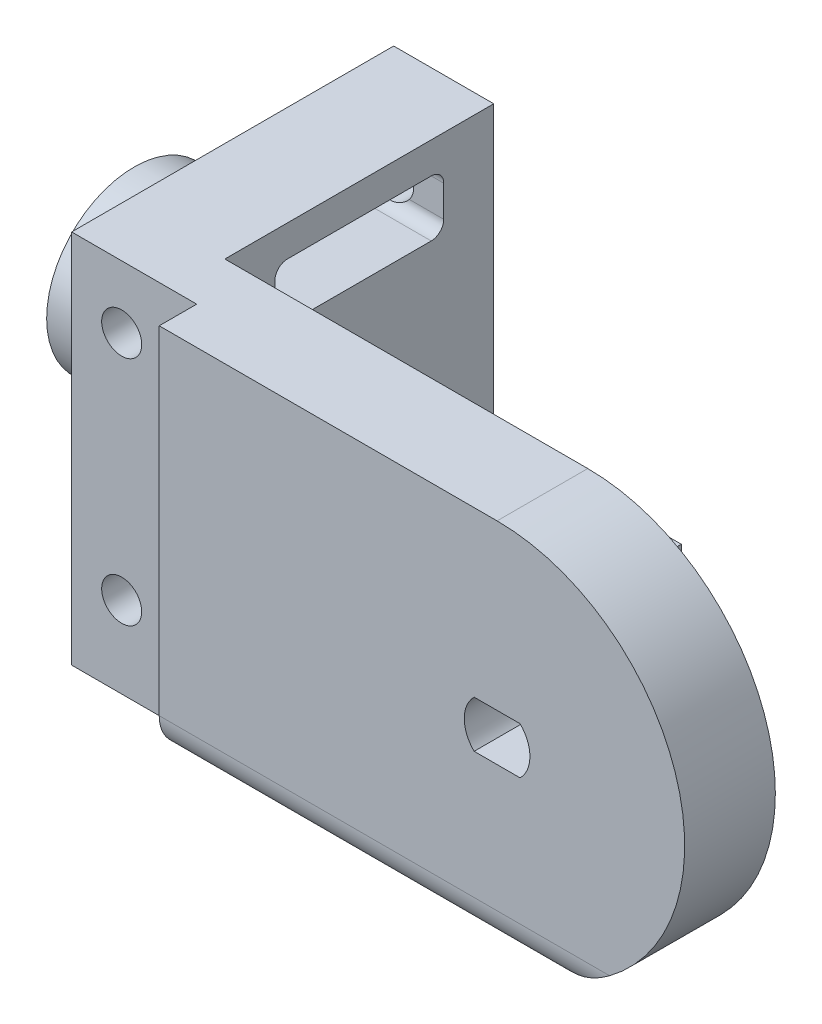
SolidWorks part; units mm, degrees
ref_plane "Front Plane" through (0, 0, 0) normal (0, 0, 1) x (1, 0, 0)
ref_plane "Top Plane" through (0, 0, 0) normal (0, 1, 0) x (1, 0, 0)
ref_plane "Right Plane" through (0, 0, 0) normal (1, 0, 0) x (0, 0, -1)
sketch "Sketch2" plane through (0, 0, -8) normal (0, 0, 1) x (1, 0, 0)
  line L0 (-25.7692, 245.1803) -> (-54.7874, 245.1803)
  line L1 (-54.7874, 245.1803) -> (-54.7874, 215.1803)
  line L2 (-54.7874, 215.1803) -> (-25.7692, 215.1803)
  arc A2 (-25.7692, 215.1803) -> (-25.7692, 245.1803) centre (-25.7692, 230.1803) ccw
  dimension "D1" = 29.0182
extrude "Boss-Extrude1" add sketch "Sketch2" along normal blind 8
sketch "Sketch3" plane through (0, 0, -28) normal (0, 0, -1) x (-1, 0, 0)
  line L3 (25.7692, 215.1803) -> (54.7874, 215.1803)
  line L4 (54.7874, 215.1803) -> (54.7874, 245.1803)
  line L5 (54.7874, 245.1803) -> (25.7692, 245.1803)
  line L6 (25.7692, 215.1803) -> (54.7874, 215.1803)
  line L7 (54.7874, 215.1803) -> (54.7874, 245.1803)
  line L8 (54.7874, 245.1803) -> (25.7692, 245.1803)
  arc A1 (25.7692, 245.1803) -> (25.7692, 215.1803) centre (25.7692, 230.1803) ccw
  arc A2 (25.7692, 245.1803) -> (25.7692, 215.1803) centre (25.7692, 230.1803) ccw
  dimension "D1" = 0
extrude "Boss-Extrude2" add sketch "Sketch3" along normal blind 8 separate body
sketch "Sketch4" plane through (-54.7874, 0, 0) normal (-1, 0, 0) x (0, 0, 1)
  line L1 (-36, 245.1803) -> (0, 245.1803)
  line L2 (-36, 245.1803) -> (-36, 215.1803)
  line L3 (-36, 215.1803) -> (0, 215.1803)
  line L4 (0, 245.1803) -> (0, 215.1803)
extrude "Boss-Extrude3" add sketch "Sketch4" along normal blind 8
sketch "Sketch5" plane through (-62.7874, 0, 0) normal (-1, 0, 0) x (0, 0, 1)
  circle A1 centre (-18, 230.1803) radius 7
  circle A2 centre (-18, 230.1803) radius 5
extrude "Boss-Extrude4" add sketch "Sketch5" along normal blind 10
chamfer "Chamfer1" distance 3 angle 45 1 edges at (-62.7874, 230.1803, -11)
sketch "Sketch6" plane through (0, 0, -36) normal (0, 0, -1) x (-1, 0, 0)
  line L0 (23.9321, 232.0553) -> (27.6063, 232.0553)
  line L1 (23.9321, 228.3053) -> (27.6063, 228.3053)
  arc A0 (23.9321, 232.0553) -> (23.9321, 228.3053) centre (25.7692, 230.1803) ccw
  arc A1 (27.6063, 228.3053) -> (27.6063, 232.0553) centre (25.7692, 230.1803) ccw
  dimension "D1" = 1.875
  dimension "D2" = 3.75
extrude "Cut-Extrude1" cut sketch "Sketch6" against normal up to surface (36 mm away) up to face at (-40.5283, 230.1803, 0)
sketch "Sketch7" plane through (-62.7874, 0, 0) normal (-1, 0, 0) x (0, 0, 1)
  line L0 (0, 215.1803) -> (0, 218.1803)
  line L1 (0, 215.1803) -> (0, 245.1803) construction
  line L2 (0, 215.1803) -> (-3, 215.1803)
  line L3 (-36, 215.1803) -> (0, 215.1803) construction
  line L4 (-18, 215.1803) -> (-18, 245.1803) construction
  line L5 (0, 245.1803) -> (-36, 245.1803) construction
  line L6 (-36, 215.1803) -> (-33, 215.1803)
  line L7 (-36, 215.1803) -> (-36, 218.1803)
  arc A0 (0, 218.1803) -> (-3, 215.1803) centre (-3, 218.1803) cw
  arc A1 (-36, 218.1803) -> (-33, 215.1803) centre (-33, 218.1803) ccw
extrude "Cut-Extrude2" cut sketch "Sketch7" against normal through all
sketch "Sketch8" plane through (0, 215.1803, 0) normal (0, -1, 0) x (1, 0, 0)
  line L0 (-54.7874, -8) -> (-25.7692, -8) construction
  line L1 (-56.7874, -28) -> (-39.7874, -28)
  line L2 (-56.7874, -28) -> (-56.7874, -8)
  line L3 (-56.7874, -8) -> (-39.7874, -8)
  line L4 (-39.7874, -28) -> (-39.7874, -8)
extrude "Boss-Extrude5" add sketch "Sketch8" against normal blind 7
sketch "Sketch10" plane through (0, 0, -28) normal (0, 0, 1) x (1, 0, 0)
  line L5 (-54.7874, 222.1803) -> (-39.7874, 222.1803)
  line L6 (-39.7874, 222.1803) -> (-39.7874, 215.1803)
  line L7 (-39.7874, 215.1803) -> (-25.7692, 215.1803)
  line L8 (-25.7692, 245.1803) -> (-54.7874, 245.1803)
  line L9 (-54.7874, 245.1803) -> (-54.7874, 222.1803)
  line L10 (-54.7874, 222.1803) -> (-39.7874, 222.1803)
  line L11 (-39.7874, 222.1803) -> (-39.7874, 215.1803)
  line L12 (-39.7874, 215.1803) -> (-25.7692, 215.1803)
  line L13 (-25.7692, 245.1803) -> (-54.7874, 245.1803)
  line L14 (-54.7874, 245.1803) -> (-54.7874, 222.1803)
  arc A1 (-25.7692, 215.1803) -> (-25.7692, 245.1803) centre (-25.7692, 230.1803) ccw
  arc A2 (-25.7692, 215.1803) -> (-25.7692, 245.1803) centre (-25.7692, 230.1803) ccw
  dimension "D1" = 0
extrude "Cut-Extrude3" cut sketch "Sketch10" against normal blind 0.75
sketch "Sketch11" plane through (0, 0, -8) normal (0, 0, -1) x (-1, 0, 0)
  line L5 (25.7692, 215.1803) -> (39.7874, 215.1803)
  line L6 (39.7874, 215.1803) -> (39.7874, 222.1803)
  line L7 (39.7874, 222.1803) -> (54.7874, 222.1803)
  line L8 (54.7874, 222.1803) -> (54.7874, 245.1803)
  line L9 (54.7874, 245.1803) -> (25.7692, 245.1803)
  line L10 (25.7692, 215.1803) -> (39.7874, 215.1803)
  line L11 (39.7874, 215.1803) -> (39.7874, 222.1803)
  line L12 (39.7874, 222.1803) -> (54.7874, 222.1803)
  line L13 (54.7874, 222.1803) -> (54.7874, 245.1803)
  line L14 (54.7874, 245.1803) -> (25.7692, 245.1803)
  arc A1 (25.7692, 245.1803) -> (25.7692, 215.1803) centre (25.7692, 230.1803) ccw
  arc A2 (25.7692, 245.1803) -> (25.7692, 215.1803) centre (25.7692, 230.1803) ccw
  dimension "D1" = 0
extrude "Cut-Extrude4" cut sketch "Sketch11" against normal blind 0.75
sketch "Sketch12" plane through (-62.7874, 0, 0) normal (-1, 0, 0) x (0, 0, 1)
  line L1 (-23.75, 242.6803) -> (-12.25, 242.6803)
  line L2 (-24.75, 241.6803) -> (-24.75, 239.1803)
  line L3 (-23.75, 238.1803) -> (-12.25, 238.1803)
  line L4 (-7.25, 245.1803) -> (-28.75, 245.1803)
  line L5 (-7.25, 222.1803) -> (-7.25, 245.1803)
  line L6 (-28.75, 222.1803) -> (-7.25, 222.1803)
  line L7 (-28.75, 245.1803) -> (-28.75, 222.1803)
  line L8 (-7.25, 245.1803) -> (-28.75, 245.1803) construction
  line L9 (-7.25, 222.1803) -> (-7.25, 245.1803) construction
  line L10 (-28.75, 222.1803) -> (-7.25, 222.1803) construction
  line L11 (-28.75, 245.1803) -> (-28.75, 222.1803) construction
  line L12 (-11.25, 241.6803) -> (-11.25, 239.1803)
  arc A0 (-12.25, 238.1803) -> (-11.25, 239.1803) centre (-12.25, 239.1803) ccw
  arc A1 (-12.25, 242.6803) -> (-11.25, 241.6803) centre (-12.25, 241.6803) cw
  arc A2 (-23.75, 242.6803) -> (-24.75, 241.6803) centre (-23.75, 241.6803) ccw
  arc A3 (-24.75, 239.1803) -> (-23.75, 238.1803) centre (-23.75, 239.1803) ccw
  point P10 (-11.25, 238.1803)
  point P13 (-11.25, 242.6803)
  dimension "D6" = 1
  dimension "D1" = 0
extrude "Cut-Extrude5" cut sketch "Sketch12" against normal through all both and the other way through all
sketch "Sketch13" plane through (0, 0, -36) normal (0, 0, -1) x (-1, 0, 0)
  line L1 (52.7874, 245.1803) -> (65.2203, 245.1803)
  line L2 (52.7874, 245.1803) -> (52.7874, 215.1803)
  line L3 (52.7874, 215.1803) -> (65.2203, 215.1803)
  line L4 (65.2203, 245.1803) -> (65.2203, 215.1803)
extrude "Cut-Extrude6" cut sketch "Sketch13" against normal blind 3
sketch "Sketch14" plane through (0, 0, 0) normal (0, 0, 1) x (1, 0, 0)
  line L4 (-52.7874, 245.1803) -> (-62.7874, 245.1803)
  line L5 (-52.7874, 215.1803) -> (-52.7874, 245.1803)
  line L6 (-62.7874, 215.1803) -> (-52.7874, 215.1803)
  line L7 (-62.7874, 245.1803) -> (-62.7874, 215.1803)
  line L8 (-52.7874, 245.1803) -> (-62.7874, 245.1803)
  line L9 (-52.7874, 215.1803) -> (-52.7874, 245.1803)
  line L10 (-62.7874, 215.1803) -> (-52.7874, 215.1803)
  line L11 (-62.7874, 245.1803) -> (-62.7874, 215.1803)
  dimension "D1" = 0
extrude "Cut-Extrude7" cut sketch "Sketch14" against normal blind 3
sketch "Sketch15" plane through (0, 0, 0) normal (0, 0, 1) x (1, 0, 0)
  spline S0 degree 3 poles (-58.7873, 241.7803) (-61.9873, 241.7803) (-61.9873, 238.5803) (-58.7873, 238.5803) (-55.5873, 238.5803) (-55.5873, 241.7803) (-58.7873, 241.7803) (-61.9873, 241.7803) (-61.9873, 238.5803) knots -0.5 0 0 0 0.5 0.5 0.5 1 1 1 1.5 1.5 1.5 weights 1 0.333333 0.333333 1 0.333333 0.333333 1 0.333333 0.333333 only from (-58.7873, 241.7803) to (-58.7873, 241.7803) construction
  spline S1 degree 3 poles (-58.7873, 223.28) (-61.9873, 223.28) (-61.9873, 220.08) (-58.7873, 220.08) (-55.5873, 220.08) (-55.5873, 223.28) (-58.7873, 223.28) (-61.9873, 223.28) (-61.9873, 220.08) knots -0.5 0 0 0 0.5 0.5 0.5 1 1 1 1.5 1.5 1.5 weights 1 0.333333 0.333333 1 0.333333 0.333333 1 0.333333 0.333333 only from (-58.7873, 223.28) to (-58.7873, 223.28) construction
  spline S2 degree 3 poles (-58.7873, 241.7803) (-61.9873, 241.7803) (-61.9873, 238.5803) (-58.7873, 238.5803) (-55.5873, 238.5803) (-55.5873, 241.7803) (-58.7873, 241.7803) (-61.9873, 241.7803) (-61.9873, 238.5803) knots -0.5 0 0 0 0.5 0.5 0.5 1 1 1 1.5 1.5 1.5 weights 1 0.333333 0.333333 1 0.333333 0.333333 1 0.333333 0.333333 only from (-58.7873, 241.7803) to (-58.7873, 241.7803)
  spline S3 degree 3 poles (-58.7873, 223.28) (-61.9873, 223.28) (-61.9873, 220.08) (-58.7873, 220.08) (-55.5873, 220.08) (-55.5873, 223.28) (-58.7873, 223.28) (-61.9873, 223.28) (-61.9873, 220.08) knots -0.5 0 0 0 0.5 0.5 0.5 1 1 1 1.5 1.5 1.5 weights 1 0.333333 0.333333 1 0.333333 0.333333 1 0.333333 0.333333 only from (-58.7873, 223.28) to (-58.7873, 223.28)
extrude "Cut-Extrude8" cut sketch "Sketch15" against normal up to surface (36 mm away) up to face at (-25.7692, 230.1803, -36)
sketch "Sketch16" plane through (0, 0, -36) normal (0, 0, -1) x (-1, 0, 0)
  line L1 (75.759, 213.0722) -> (7.7191, 213.0722)
  line L2 (75.759, 213.0722) -> (75.759, 247.053)
  line L3 (75.759, 247.053) -> (7.7191, 247.053)
  line L4 (7.7191, 213.0722) -> (7.7191, 247.053)
extrude "Cut-Extrude9" cut sketch "Sketch16" against normal up to surface (7.25 mm away) up to face at (-37.6147, 227.5136, -28.75)
